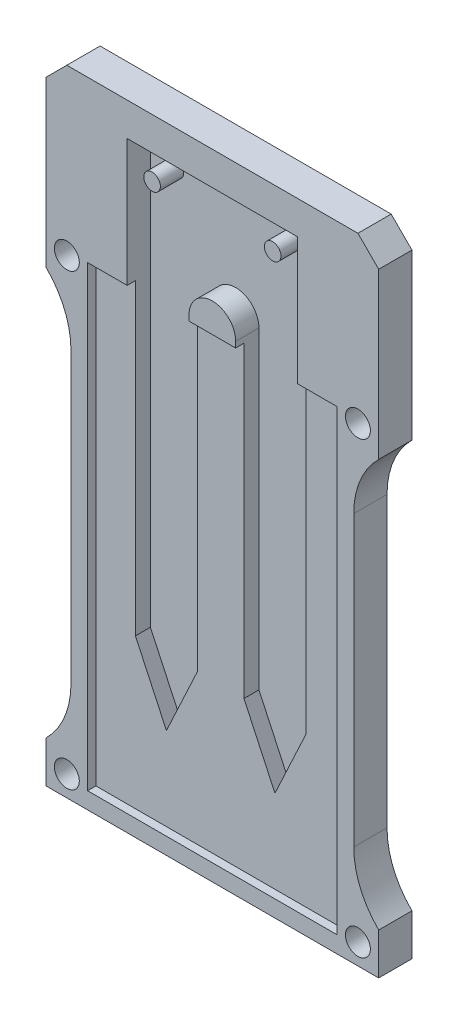
SolidWorks part; units mm, degrees
ref_plane "Alzado" through (0, 0, 0) normal (1, 0, 0) x (0, 1, 0)
ref_plane "Planta" through (0, 0, 0) normal (0, 0, 1) x (0, 1, 0)
ref_plane "Vista lateral" through (0, 0, 0) normal (0, 1, 0) x (-1, 0, 0)
sketch "Croquis2" plane through (0, 0, 0) normal (0, 0, 1) x (0, 1, 0)
  line L0 (-24.5, 20) -> (-24.5, 17)
  line L1 (-29.5, -20) -> (-24.5, -20)
  line L2 (-29.5, -20) -> (-29.5, 20)
  line L3 (-29.5, 20) -> (-24.5, 20)
  line L4 (29.5, -20) -> (29.5, -10.25)
  line L5 (-29.5, -20) -> (29.5, 20) construction
  line L6 (-29.5, 20) -> (29.5, -20) construction
  line L7 (-24.5, 17) -> (24.5, 17)
  line L8 (24.5, 17) -> (24.5, 20)
  line L9 (-24.5, -20) -> (-24.5, -17)
  line L10 (-24.5, -17) -> (24.5, -17)
  line L11 (24.5, -17) -> (24.5, -20)
  line L12 (24.5, 20) -> (29.5, 20)
  line L13 (24.5, -20) -> (29.5, -20)
  line L14 (29.5, -15) -> (42.8, -15)
  line L15 (-27.5, -15) -> (27.5, -15)
  line L16 (-27.5, -15) -> (-27.5, 15)
  line L17 (-27.5, 15) -> (27.5, 15)
  line L18 (27.5, -15) -> (27.5, 15)
  line L19 (-27.5, -15) -> (27.5, 15) construction
  line L20 (-27.5, 15) -> (27.5, -15) construction
  line L21 (42.8, -10.25) -> (42.8, 10.25)
  line L22 (42.8, 15) -> (29.5, 15)
  line L23 (-17.5, -15) -> (-17.5, 15)
  line L24 (29.5, -20) -> (46.8, -20)
  line L25 (46.8, -20) -> (46.8, 20)
  line L26 (46.8, 20) -> (29.5, 20)
  line L27 (42.8, 10.25) -> (-9.5, 10.25)
  line L28 (42.8, -10.25) -> (-9.5, -10.25)
  line L29 (0, 0) -> (-17.5, 0) construction
  line L31 (28.2, 2.8) -> (-9.5, 2.8)
  line L32 (28.2, -2.8) -> (-9.5, -2.8)
  line L33 (-9.5, 2.8) -> (-17.5, 6.525)
  line L34 (42.8, 10.25) -> (42.8, 15)
  line L35 (42.8, -10.25) -> (42.8, -15)
  line L36 (-17.5, 6.525) -> (-9.5, 10.25)
  line L37 (-9.5, -2.8) -> (-17.5, -6.525)
  line L38 (-17.5, -6.525) -> (-9.5, -10.25)
  line L39 (29.5, 10.25) -> (29.5, 20)
  circle A0 centre (27, 17.5) radius 1.5
  circle A2 centre (-27, -17.5) radius 1.5
  circle A3 centre (-27, 17.5) radius 1.5
  circle A4 centre (27, -17.5) radius 1.5
  arc A5 (28.2, 2.8) -> (28.2, -2.8) centre (28.2, 0) cw
  circle A9 centre (39.8, 7.25) radius 1
  circle A10 centre (39.8, -7.25) radius 1
  point P0 (0, 0)
  point P14 (0, 0)
  point P19 (-24.5, 18.5)
  point P20 (-27, 17.5)
  point P21 (27, 17.5)
  point P22 (27, -17.5)
  point P23 (-27, -17.5)
  point P42 (27.5, -10.25)
  point P45 (27.5, 0)
  point P50 (0, 0)
  point P52 (31, 0)
  point P63 (-17.5, 6.525)
  point P72 (27.5, 10.25)
  dimension "D10" = 3
  dimension "D20" = 2
  dimension "D16" = 2.8
  dimension "D1" = 59
  dimension "D2" = 40
  dimension "D5" = 30
  dimension "D3" = 2
  dimension "D4" = 5
  dimension "D6" = 2.5
  dimension "D8" = 2.5
  dimension "D9" = 2.5
  dimension "D11" = 55
  dimension "D7" = 2.5
  dimension "D13" = 10
  dimension "D12" = 60.3
  dimension "D15" = 20.5
  dimension "D17" = 5.6
  dimension "D21" = 3
  dimension "D22" = 3
  dimension "D23" = 3
  dimension "D14" = 4
  dimension "D24" = 7.45
  dimension "D25" = 3.725
  dimension "D26" = 8
  dimension "D18" = 48.5
extrude "Saliente-Extruir4" add sketch "Croquis2" along normal blind 4 contours L4 L28 L18 L15 L16 L17 L27 L12 L8 L7 L0 L3 L2 L1 L9 L10 L11 L13 A4 A3 A2 A0 | L21 L35 L14 L4 L24 L25 L26 L22 L34 | L28 L4 L14 L35 | L27 L34 L22 L4 | A5 L18 | A9 | A10 region at (-18.5, -25.2128, 0) region at (-19.5642, 38.15, 0) region at (-12.625, 36.15, 0) region at (12.625, 36.15, 0) region at (0, 29.0169, 0) region at (-7.25, 39.8, 0) region at (7.25, 39.8, 0)
extrude "Saliente-Extruir5" add sketch "Croquis2<7>" along normal blind 3 contours L15 L23 L17 L16 | L27 L18 L17 L23 | L32 L18 L31 L23 | L18 L28 L23 L15 region at (-12.3893, 3.7076, 0) region at (0, 2.9026, 0) region at (0, -22.5, 0) region at (12.3893, 3.7076, 0)
sketch "Croquis2<7>" plane through (0, 0, 0) normal (0, 0, 1) x (0, 1, 0) same geometry as "Croquis2"
extrude "Saliente-Extruir6" add sketch "Croquis2<8>" along normal blind 1.2 contours L37 L38 L28 L18 L32 | L36 L33 L31 L18 L27 | L18 A5 L28 L21 L27 A10 A9 region at (0, 35.3917, 0) region at (-6.525, 6.935, 0) region at (6.525, 6.935, 0)
sketch "Croquis2<8>" plane through (0, 0, 0) normal (0, 0, 1) x (0, 1, 0) same geometry as "Croquis2"
fillet "Redondeo2" radius 10 4 edges at (17, -24.5, 2) (17, 24.5, 2) (-17, -24.5, 2) (-17, 24.5, 2)
chamfer "Chaflán2" distance 2.5 angle 45 2 edges at (-20, 46.8, 2) (20, 46.8, 2)
equation "\"D25@Croquis2\"=\"D24@Croquis2\"/2"
